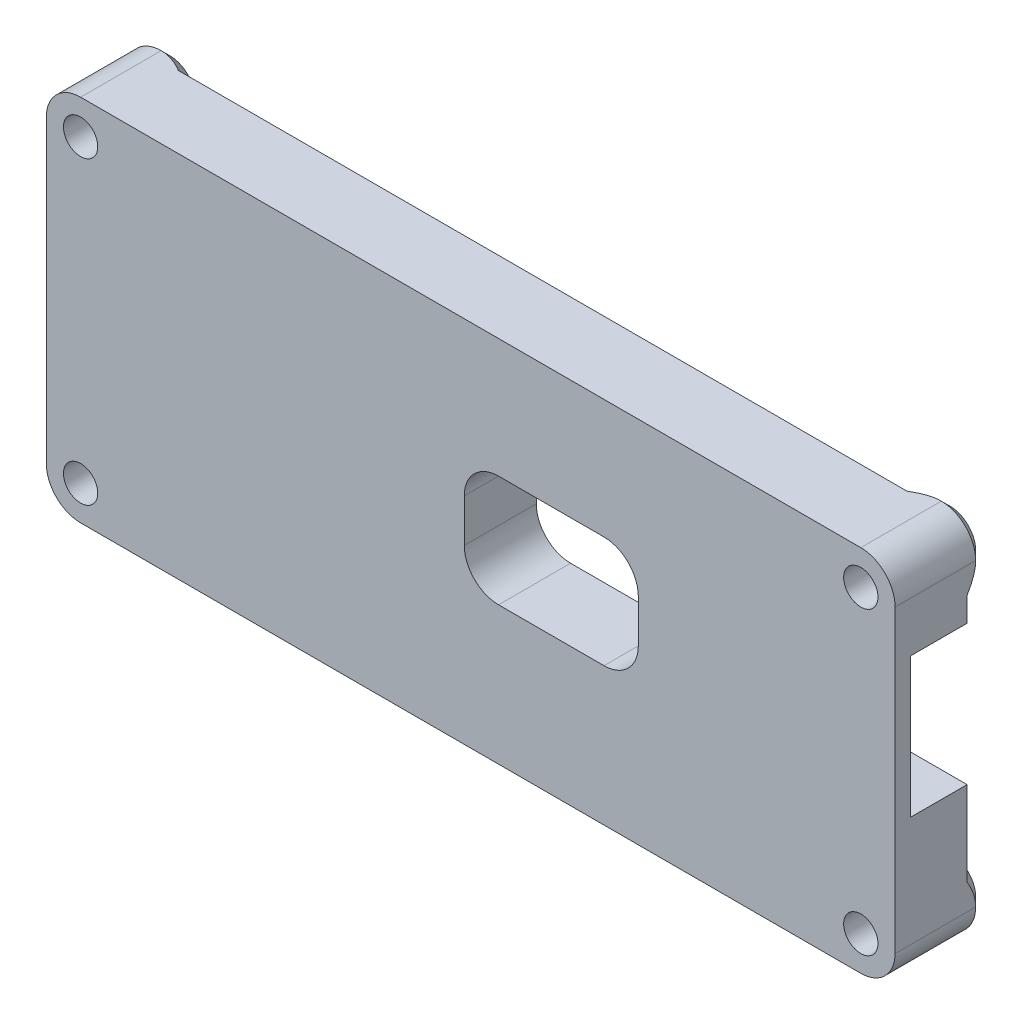
SolidWorks part; units mm, degrees
ref_plane "Front Plane" through (0, 0, 0) normal (0, 0, 1) x (1, 0, 0)
ref_plane "Top Plane" through (0, 0, 0) normal (0, 1, 0) x (1, 0, 0)
ref_plane "Right Plane" through (0, 0, 0) normal (1, 0, 0) x (0, 0, -1)
ref_plane "Plane1" through (0, 0, 2) normal (0, 0, 1) x (1, 0, 0)
sketch "Sketch3" plane through (0, 0, 2) normal (0, 0, 1) x (1, 0, 0)
  line L1 (-99, 43) -> (0, 43)
  line L2 (-99, 43) -> (-99, 0)
  line L3 (-99, 0) -> (0, 0)
  line L4 (0, 43) -> (0, 0)
  line L5 (-49.5, 0) -> (-49.5, 43) construction
  line L6 (-99, 21.5) -> (0, 21.5) construction
  circle A0 centre (-95, 39) radius 2
  circle A1 centre (-95, 4) radius 2
  circle A2 centre (-4, 4) radius 2
  circle A3 centre (-4, 39) radius 2
  point P0 (-95, 39)
  point P1 (-95, 4)
  point P3 (-4, 4)
  point P5 (-4, 39)
  point P180 (-49.5, 21.5)
  dimension "D1" = 4
extrude "Boss-Extrude2" add sketch "Sketch3" along normal offset from surface (8.4 mm away) 2 offset beyond the face yes
sketch "Sketch4" plane through (0, 0, 2) normal (0, 0, -1) x (-1, 0, 0)
  circle A0 centre (4, 39) radius 3
  circle A1 centre (95, 39) radius 3
  circle A2 centre (95, 4) radius 3
  circle A3 centre (4, 4) radius 3
  circle A4 centre (95, 4) radius 2 construction
  circle A5 centre (95, 39) radius 2 construction
  circle A6 centre (4, 39) radius 2 construction
  circle A7 centre (4, 4) radius 2 construction
  circle A8 centre (95, 4) radius 2
  circle A9 centre (95, 39) radius 2
  circle A10 centre (4, 39) radius 2
  circle A11 centre (4, 4) radius 2
  dimension "D1" = 6
extrude "Boss-Extrude3" add sketch "Sketch4" along normal up to surface (2 mm away)
chamfer "Chamfer1" distance 2 angle 45 4 edges at (-92, 39, 2) (-1, 39, 2) (-92, 4, 2) (-1, 4, 2)
sketch "Sketch5" plane through (0, 0, 0) normal (1, 0, 0) x (0, 0, -1)
  line L1 (-8.6, 33.163) -> (0, 33.163)
  line L2 (-8.6, 33.163) -> (-8.6, 16.863)
  line L3 (-8.6, 16.863) -> (0, 16.863)
  line L4 (0, 33.163) -> (0, 16.863)
  line L5 (-4.3, 16.863) -> (-4.3, 33.163) construction
  line L6 (-8.6, 25.013) -> (0, 25.013) construction
  line L8 (0, 0) -> (0, 43) construction
  point P120 (-4.3, 25.013)
  dimension "D1" = 0.2
  dimension "D2" = 0.4
  dimension "D3" = 0.4
extrude "Cut-Extrude1" cut sketch "Sketch5" against normal offset from surface (19.391 mm away) 1 offset beyond the face yes
sketch "Sketch6" plane through (0, 0, 2) normal (0, 0, -1) x (-1, 0, 0)
  line L1 (50.25, 16.1) -> (29.95, 16.1)
  line L2 (50.25, 16.1) -> (50.25, 29.1)
  line L3 (50.25, 29.1) -> (29.95, 29.1)
  line L4 (29.95, 16.1) -> (29.95, 29.1)
  line L5 (40.1, 29.1) -> (40.1, 16.1) construction
  line L6 (50.25, 22.6) -> (29.95, 22.6) construction
  point P184 (40.1, 22.6)
  dimension "D1" = 2
  dimension "D2" = 2
  dimension "D3" = 2
  dimension "D4" = 2
extrude "Cut-Extrude2" cut sketch "Sketch6" against normal up to next
fillet "Fillet1" radius 4 8 edges at (-50.25, 16.1, 6.2) (-50.25, 29.1, 6.2) (-29.95, 29.1, 6.2) (-29.95, 16.1, 6.2) (-99, 0, 6.2) (0, 0, 6.2) (0, 43, 6.2) (-99, 43, 6.2)
